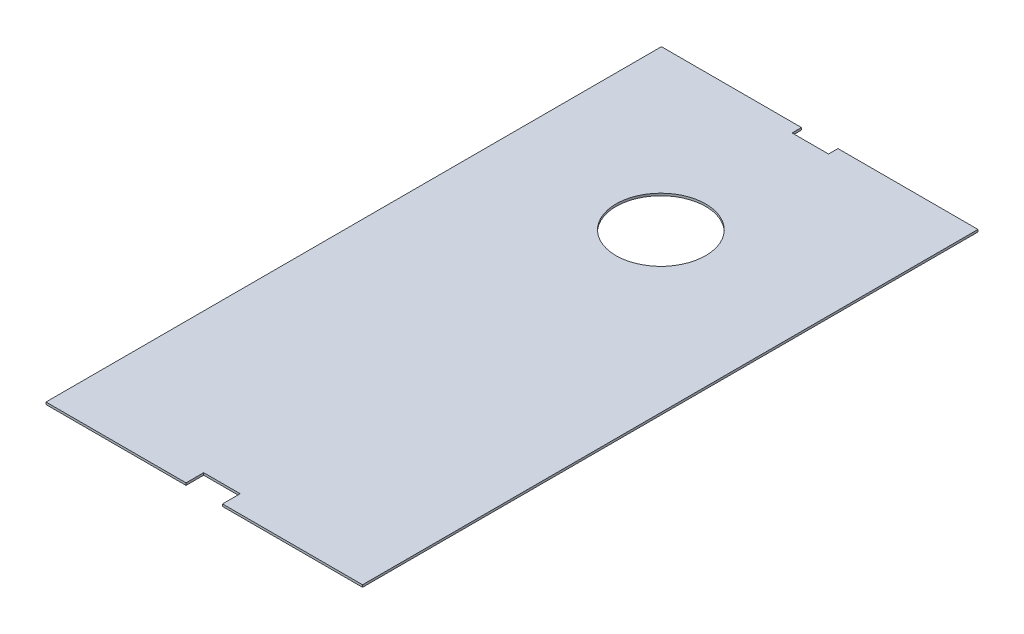
SolidWorks part; units mm, degrees
ref_plane "Front Plane" through (0, 0, 0) normal (0, 0, 1) x (1, 0, 0)
ref_plane "Top Plane" through (0, 0, 0) normal (0, 1, 0) x (1, 0, 0)
ref_plane "Right Plane" through (0, 0, 0) normal (1, 0, 0) x (0, 0, -1)
sketch "BaseSketch" plane through (0, 0, 0) normal (0, 1, 0) x (1, 0, 0)
  line L0 (0, -55) -> (0, 55) construction
  line L1 (-254, -508) -> (254, -508)
  line L2 (-254, -508) -> (-254, 508)
  line L3 (-254, 508) -> (254, 508)
  line L4 (254, -508) -> (254, 508)
  line L5 (-254, -508) -> (254, 508) construction
  line L6 (-254, 508) -> (254, -508) construction
  point P0 (0, 0)
  dimension "D1" = 90
extrude "Boss-Extrude1" add sketch "BaseSketch" along normal blind 3.81
sketch "Sketch7" plane through (0, 3.81, 0) normal (0, 1, 0) x (1, 0, 0)
  line L8 (269, -523) -> (269, 523)
  line L9 (269, 523) -> (-269, 523)
  line L10 (-269, 523) -> (-269, -523)
  line L11 (-269, -523) -> (269, -523)
  line L12 (269, -523) -> (269, 523)
  line L13 (269, 523) -> (-269, 523)
  line L14 (-269, 523) -> (-269, -523)
  line L15 (-269, -523) -> (269, -523)
  dimension "D1" = 15
extrude "Boss-Extrude2" add sketch "Sketch7" against normal up to surface (3.81 mm away) up to face at (0, 0, 0)
sketch "TabCutSketch" plane through (0, 3.81, 0) normal (0, 1, 0) x (1, 0, 0)
  line L1 (-31, -523) -> (31, -523)
  line L2 (-31, -523) -> (-31, -493)
  line L3 (-31, -493) -> (31, -493)
  line L4 (31, -523) -> (31, -493)
  line L5 (-269, -523) -> (269, -523) construction
  line L10 (0, 0) -> (0, 507) construction
  line L11 (0, 507) -> (0, 0) construction
  line L13 (31, 523) -> (-31, 523)
  line L14 (31, 523) -> (31, 507)
  line L15 (31, 507) -> (-31, 507)
  line L16 (-31, 523) -> (-31, 507)
  line L17 (0, 0) -> (0, -493) construction
  line L18 (269, 523) -> (-269, 523) construction
  point P0 (0, -523)
  point P5 (0, 0)
  point P8 (0, 0)
  point P17 (31, -507)
  dimension "D1" = 30
  dimension "D2" = 62
  dimension "D3" = 16
  dimension "D4" = 62
extrude "Cut-Extrude1" cut sketch "TabCutSketch" against normal through all
sketch "Sketch6" plane through (0, 3.81, 0) normal (0, 1, 0) x (1, 0, 0)
  line L0 (0, 253) -> (0, 507) construction
  line L2 (-31, 507) -> (31, 507) construction
  circle A0 centre (0, 253) radius 76.2
  dimension "D2" = 152.4
  dimension "D1" = 254
extrude "Cut-Extrude10" cut sketch "Sketch6" against normal blind 3.81
